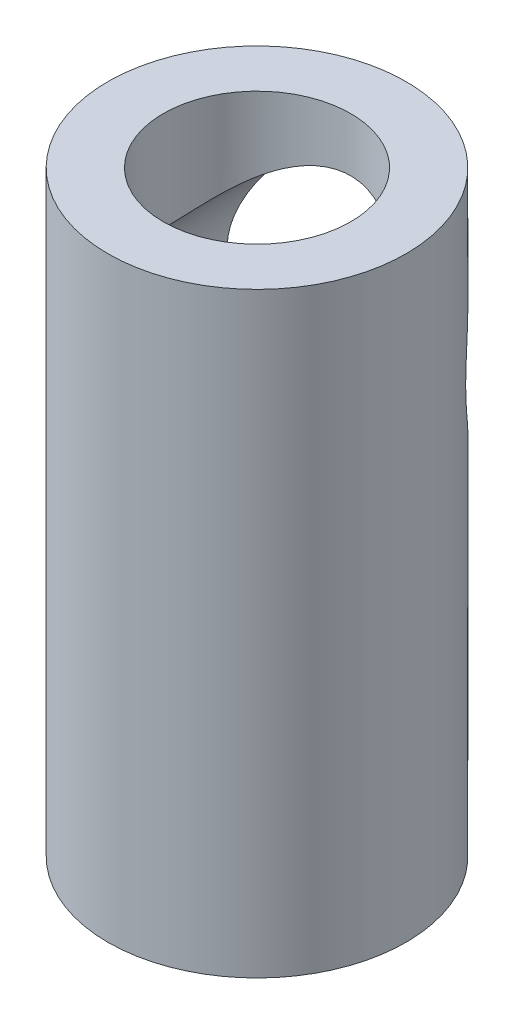
SolidWorks part; units mm, degrees
material "6061-T6 (SS)"
ref_plane "Front Plane" through (0, 0, 0) normal (0, 0, 1) x (1, 0, 0)
ref_plane "Top Plane" through (0, 0, 0) normal (0, 1, 0) x (1, 0, 0)
ref_plane "Right Plane" through (0, 0, 0) normal (1, 0, 0) x (0, 0, -1)
sketch "Sketch1" plane through (0, 0, 0) normal (0, 1, 0) x (1, 0, 0)
  circle A0 centre (0, 0) radius 1.9964
  circle A1 centre (0, 0) radius 3.175
  dimension "D1" = 3.9929
  dimension "D2" = 6.35
extrude "Boss-Extrude1" add sketch "Sketch1" along normal blind 12.7
sketch "Sketch2" plane through (0, 12.7, 0) normal (0, 1, 0) x (1, 0, 0)
  line L0 (0, 0) -> (0, 3.175)
  circle A0 centre (0, 0) radius 3.175 construction
ref_plane "Plane1" through (0, 12.7, -3.175) normal (0, 0, -1) x (-1, 0, 0)
sketch "Sketch4" plane through (0, 12.7, -3.175) normal (0, 0, -1) x (-1, 0, 0)
  line L0 (3.175, 0) -> (-3.175, 0) construction
  circle A0 centre (0, -3.6881) radius 2.54
  dimension "D1" = 3.6881
extrude "Cut-Extrude1" cut sketch "Sketch4" against normal blind 3.175
